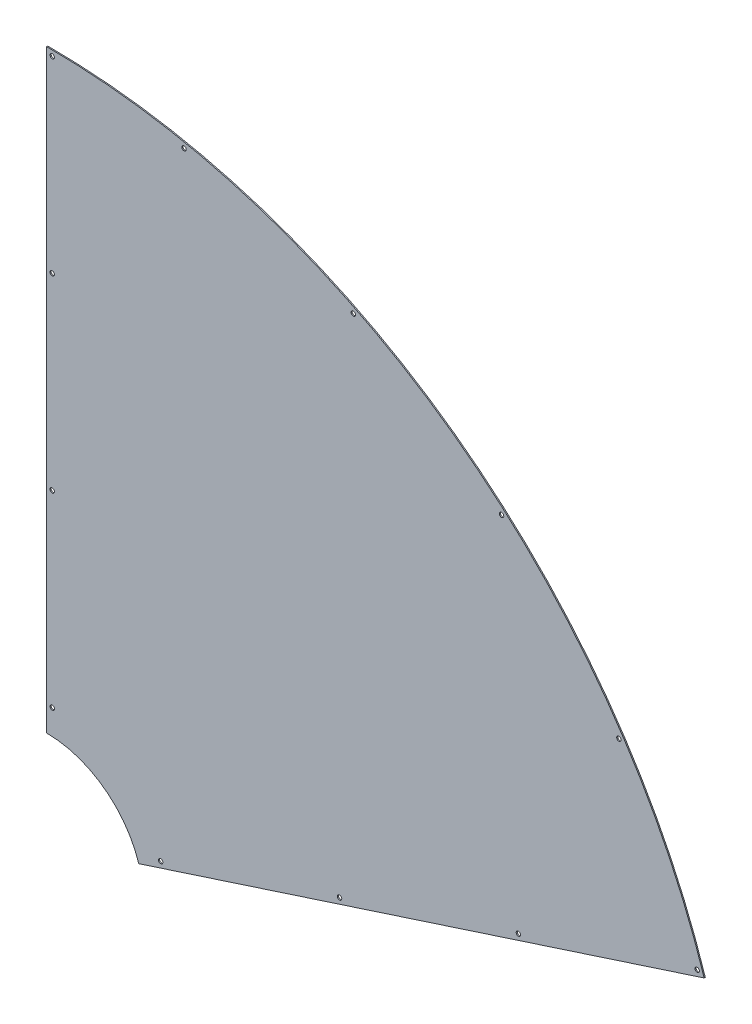
SolidWorks part; units mm, degrees
material "Galvanized Steel"
ref_plane "Front Plane" through (0, 0, 0) normal (0, 0, 1) x (1, 0, 0)
ref_plane "Top Plane" through (0, 0, 0) normal (0, 1, 0) x (1, 0, 0)
ref_plane "Right Plane" through (0, 0, 0) normal (1, 0, 0) x (0, 0, -1)
sketch "Sketch1" plane through (0, 0, 0) normal (0, 0, 1) x (1, 0, 0)
  line L0 (0, 1250) -> (0, 175)
  line L1 (166.5365, 53.7642) -> (1188.9225, 385.9576)
  arc A0 (1188.9225, 385.9576) -> (0, 1250) centre (0, 0) ccw
  arc A1 (166.5365, 53.7642) -> (0, 175) centre (0, 0) ccw
  circle A3 centre (206.0868, 77.5436) radius 4
  circle A4 centre (529.5675, 182.2348) radius 4
  circle A5 centre (852.9267, 287.3006) radius 4
  circle A6 centre (10, 219.9597) radius 4
  circle A7 centre (10, 559.9597) radius 4
  circle A8 centre (10, 899.9597) radius 4
  circle A9 centre (10, 1239.9597) radius 4
  circle A10 centre (1176.286, 392.3664) radius 4
  dimension "D5" = 8
  dimension "D18" = 10
extrude "Boss-Extrude1" add sketch "Sketch1" along normal blind 2
pattern_circular "CirPattern1" count 5 every 15 about axis through (0, 0, 2) along (0, 0, 1) of face at (1180.286, 392.3664, 2)
